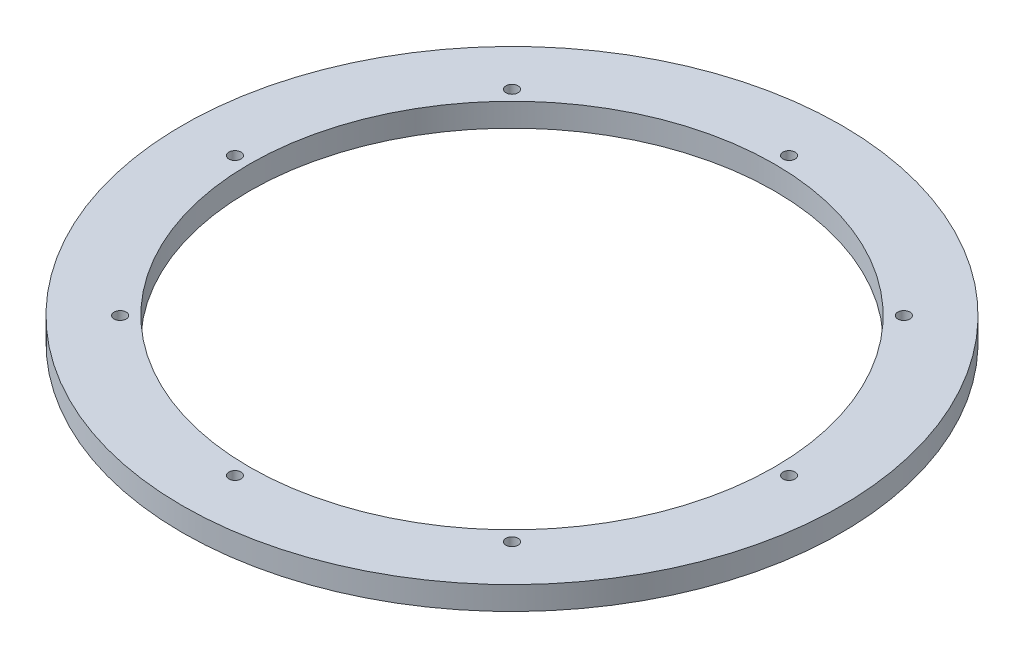
SolidWorks part; units mm, degrees
material "6061 Alloy"
ref_plane "Front Plane" through (0, 0, 0) normal (0, 0, 1) x (1, 0, 0)
ref_plane "Top Plane" through (0, 0, 0) normal (0, 1, 0) x (1, 0, 0)
ref_plane "Right Plane" through (0, 0, 0) normal (1, 0, 0) x (0, 0, -1)
sketch "Sketch1" plane through (0, 0, 0) normal (0, 1, 0) x (1, 0, 0)
  circle A0 centre (0, 0) radius 57.15
  circle A1 centre (0, 0) radius 71.755
  circle A2 centre (0, 0) radius 68.58
  circle A3 centre (0, -60.325) radius 1.3208
  circle A4 centre (-42.6562, -42.6562) radius 1.3208
  circle A5 centre (-60.325, 0) radius 1.3208
  circle A6 centre (-42.6562, 42.6562) radius 1.3208
  circle A7 centre (0, 60.325) radius 1.3208
  circle A8 centre (42.6562, 42.6562) radius 1.3208
  circle A9 centre (60.325, 0) radius 1.3208
  circle A10 centre (42.6562, -42.6562) radius 1.3208
  point P21 (0, 0)
  dimension "D1" = 114.3
  dimension "D4" = 2.6416
  dimension "D5" = 60.325
  dimension "D2" = 14.605
  dimension "D3" = 11.43
  dimension "D6" = 8
extrude "Boss-Extrude1" add sketch "Sketch1" along normal blind 5.08 contours A2 A0 | A1 A2 region at (-69.7255, 0, 0) region at (-66.6403, 0, 0)
sketch "Sketch2" plane through (0, 0, 0) normal (1, 0, 0) x (0, 0, -1)
  line L0 (-71.755, 0) -> (71.755, 0) construction
  line L1 (71.755, 5.08) -> (-71.755, 5.08) construction
  line L2 (-71.755, 0) -> (71.755, 0)
  line L3 (71.755, 5.08) -> (-71.755, 5.08)
  line L4 (89.5975, 4.318) -> (99.9841, 4.318) construction
  line L5 (95.9885, 2.54) -> (99.6739, 2.54) construction
  line L6 (0, 0) -> (0, 18.217) construction
  circle A0 centre (68.58, 5.9055) radius 1.5875 construction
  circle A1 centre (68.58, 5.969) radius 1.651
  circle A2 centre (68.58, -0.889) radius 1.651
  dimension "D3" = 3.175
  dimension "D4" = 3.302
  dimension "D1" = 68.58
  dimension "D2" = 0.762
  dimension "D5" = 2.54
equation "\"Middle Coupler Inner Daimeter\"= 4.5in"
equation "\"Middle Coupler  Wall Thickness\" = 0.25in"
equation "\"Middle Coupler Bottom Thickness\"= 0.2in"
equation "\"Bearing Rail Offset\"= 0.45in"
equation "\"3-56 UNF Tap\"= 0.089in"
equation "\"3-56 UNF Clearance\"= 0.104in"
equation "\"D5@Sketch1\"=(\"Middle Coupler Inner Daimeter\"*2+0.5)/4in"
equation "\"Ball Bearing Distance\"= 0.03in"
equation "\"D1@Sketch2\"=\"Middle Coupler Inner Daimeter\"/2+\"Bearing Rail Offset\""
equation "\"D3@Sketch1\"=\"Bearing Rail Offset\""
equation "\"D4@Sketch1\"=\"3-56 UNF Clearance\""
equation "\"D1@Sketch1\"=\"Middle Coupler Inner Daimeter\""
equation "\"D2@Sketch2\"=\"Ball Bearing Distance\""
equation "\"D4@Sketch2\"=\"D3@Sketch2\"+0.005"
equation "\"D5@Sketch2\"=\"Middle Coupler Bottom Thickness\"/2"
equation "\"TCA Outer Diameter\" = 6.625in"
equation "\"Interstage Aeroframe Wall Thickness\" = 0.072in"
equation "\"Compression Spring OD\"= 0.42in"
equation "\"10-24 Tap\"= 0.157in"
equation "\"10-24 Clearance\"= 0.196in"
equation "\"Lower Stage Fuselage Wall Thickness\" = 0.25in"
equation "\"6-32 Tap\" = 0.107in"
equation "\"1/4-20 Tap\" = 0.201in"
